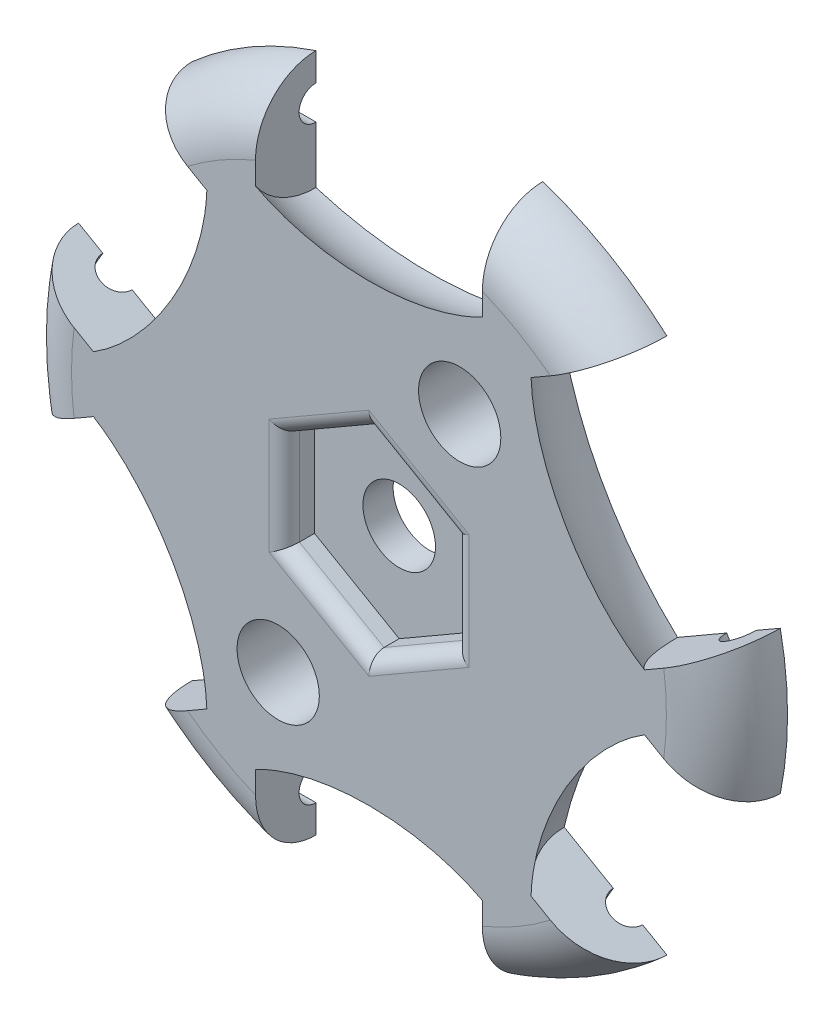
SolidWorks part; units mm, degrees
ref_plane "Front Plane" through (0, 0, 0) normal (0, 0, 1) x (1, 0, 0)
ref_plane "Top Plane" through (0, 0, 0) normal (0, 1, 0) x (1, 0, 0)
ref_plane "Right Plane" through (0, 0, 0) normal (1, 0, 0) x (0, 0, -1)
sketch "Sketch1" plane through (0, 0, 0) normal (0, 0, 1) x (1, 0, 0)
  circle A0 centre (0, 0) radius 18.796
  dimension "D1" = 37.592
extrude "Boss-Extrude1" add sketch "Sketch1" along normal blind 3.175
fillet "Fillet1" radius 3.1852 1 edges at (18.796, 0, 3.175)
sketch "Sketch2" plane through (0, 0, 3.175) normal (0, 0, 1) x (1, 0, 0)
  line L0 (-4.7625, -8.2489) -> (4.7625, 8.2489) construction
  line L1 (0, 0) -> (0, 6.4682) construction
  circle A0 centre (4.7625, 8.2489) radius 2.159
  circle A1 centre (-4.7625, -8.2489) radius 2.159
  circle A4 centre (0, 0) radius 1.905
  point P9 (0, 0)
  dimension "D2" = 4.318
  dimension "D4" = 3.81
  dimension "D1" = 9.525
  dimension "D5" = 30
  dimension "D3" = 2
extrude "Cut-Extrude1" cut sketch "Sketch2" against normal through all
sketch "Sketch5" plane through (0, 0, 0) normal (0, 0, 1) x (1, 0, 0)
  line L0 (-5.9531, 15.4686) -> (5.9531, 15.4686)
  line L1 (5.9531, 15.4686) -> (5.9531, 19.3354)
  line L2 (-5.9531, 15.4686) -> (-5.9531, 19.3354)
  line L3 (-5.9531, 15.4686) -> (-8.5086, 15.4686) construction
  arc A0 (-5.9531, 19.3354) -> (5.9531, 19.3354) centre (0, 0) cw
  circle A1 centre (0, 0) radius 18.796 construction
  point P5 (0, 15.4686)
  point P9 (0, 20.2311)
  dimension "D1" = 11.9062
  dimension "D2" = 15.4686
  dimension "D3" = 9.525
revolve "Cut-Revolve1" cut sketch "Sketch5" angle 360 about L3
sketch "Sketch6" plane through (0, 0, 0) normal (1, 0, 0) x (0, 0, -1)
  line L0 (0, -18.796) -> (0, 17.8283) construction
  circle A0 centre (0, 15.4686) radius 0.889
  arc A1 (-3.175, 13.2614) -> (0, 11.6018) centre (0, 15.4686) ccw construction
  dimension "D1" = 1.778
extrude "Cut-Extrude2" cut sketch "Sketch6" against normal mid plane 15.875
pattern_circular "CirPattern1" count 6 over 360 about axis through (0, 0, 0) along (0, 0, 1) of "Cut-Revolve1", "Cut-Extrude2"
sketch "Sketch8" plane through (0, 0, 3.175) normal (0, 0, 1) x (1, 0, 0)
  line L1 (0, 5.1326) -> (-4.445, 2.5663)
  line L2 (-4.445, 2.5663) -> (-4.445, -2.5663)
  line L3 (-4.445, -2.5663) -> (0, -5.1326)
  line L4 (0, -5.1326) -> (4.445, -2.5663)
  line L5 (4.445, -2.5663) -> (4.445, 2.5663)
  line L6 (4.445, 2.5663) -> (0, 5.1326)
  circle A0 centre (0, 0) radius 4.445 construction
  dimension "D1" = 8.89
extrude "Cut-Extrude4" cut sketch "Sketch8" against normal blind 1.5875
fillet "Fillet2" radius 0.7937 6 edges at (-2.2225, 3.8495, 3.175) (-4.445, 0, 3.175) (-2.2225, -3.8495, 3.175) (2.2225, -3.8495, 3.175) (4.445, 0, 3.175) (2.2225, 3.8495, 3.175)
